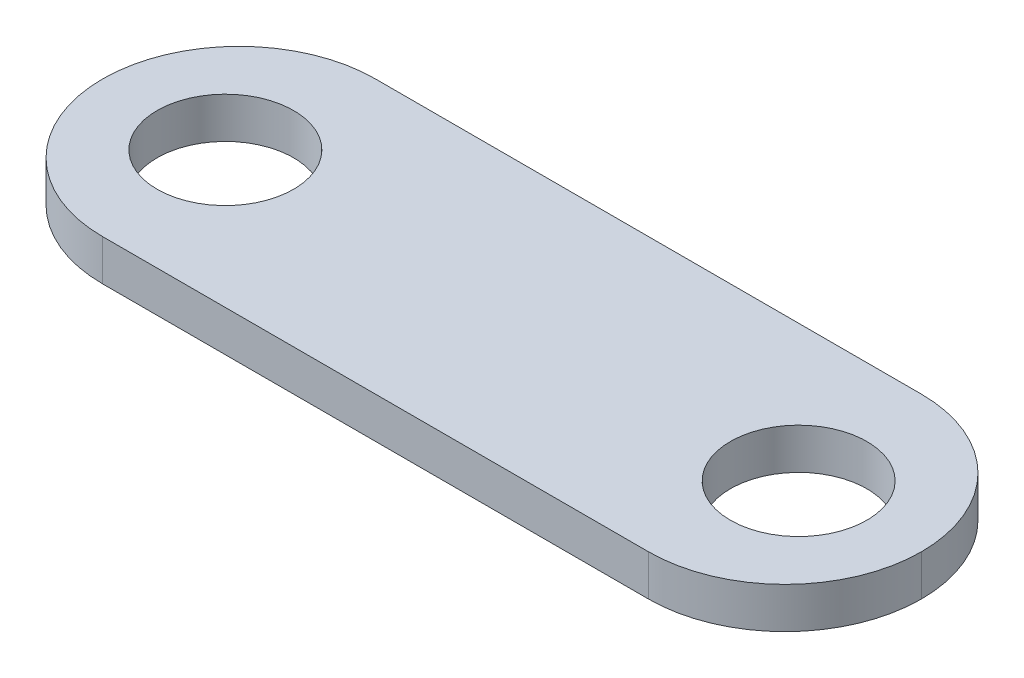
SolidWorks part; units mm, degrees
ref_plane "Front Plane" through (0, 0, 0) normal (0, 0, 1) x (1, 0, 0)
ref_plane "Top Plane" through (0, 0, 0) normal (0, 1, 0) x (1, 0, 0)
ref_plane "Right Plane" through (0, 0, 0) normal (1, 0, 0) x (0, 0, -1)
sketch "Sketch2" plane through (0, 0, 0) normal (0, 1, 0) x (1, 0, 0)
  line L1 (0, 0) -> (60, 0)
  line L2 (0, 0) -> (0, 20)
  line L3 (0, 20) -> (60, 20)
  line L4 (60, 0) -> (60, 20)
  dimension "D1" = 60
  dimension "D2" = 20
extrude "Boss-Extrude1" add sketch "Sketch2" along normal blind 3
sketch "Sketch3" plane through (0, 3, 0) normal (0, 1, 0) x (1, 0, 0)
  line L0 (60, 20) -> (0, 20) construction
  line L1 (0, 20) -> (0, 0) construction
  circle A0 centre (9, 10) radius 5
  dimension "D1" = 10
  dimension "D2" = 9
extrude "Cut-Extrude1" cut sketch "Sketch3" against normal through all
sketch "Sketch4" plane through (0, 3, 0) normal (0, 1, 0) x (1, 0, 0)
  line L0 (60, 20) -> (0, 20) construction
  line L1 (60, 0) -> (60, 20) construction
  circle A0 centre (51, 10) radius 5
  dimension "D1" = 10
  dimension "D2" = 9
extrude "Cut-Extrude2" cut sketch "Sketch4" against normal through all
fillet "Fillet1" radius 10 2 edges at (0, 1.5, -20) (0, 1.5, 0)
fillet "Fillet2" radius 10 2 edges at (60, 1.5, -20) (60, 1.5, 0)
